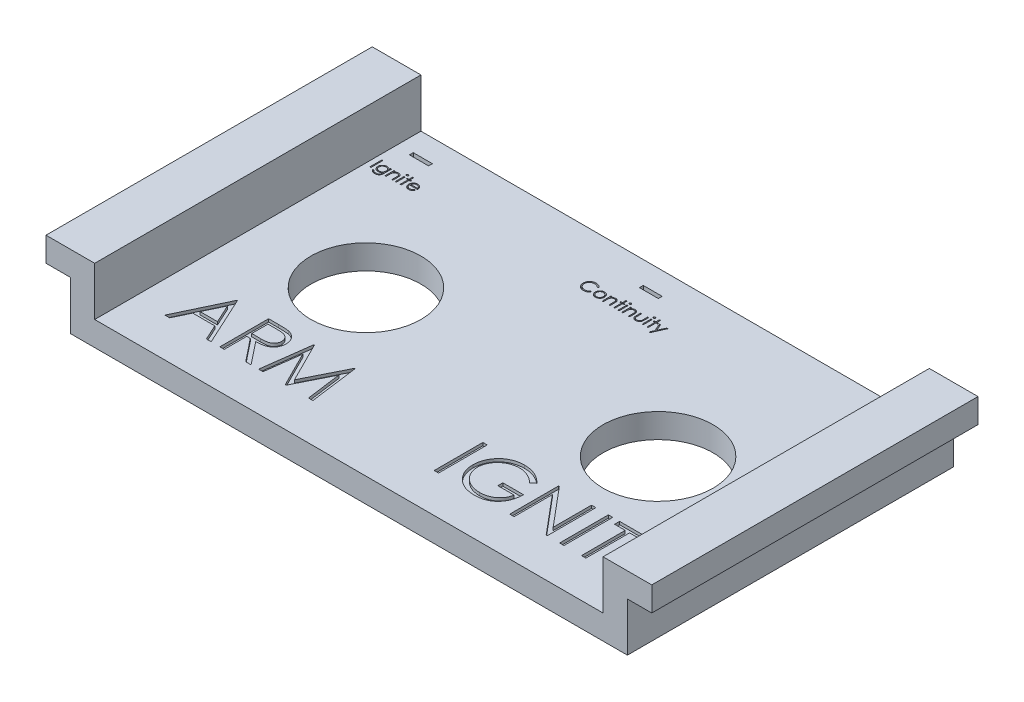
SolidWorks part; units mm, degrees
ref_plane "Front Plane" through (0, 0, 0) normal (0, 0, 1) x (1, 0, 0)
ref_plane "Top Plane" through (0, 0, 0) normal (0, 1, 0) x (1, 0, 0)
ref_plane "Right Plane" through (0, 0, 0) normal (1, 0, 0) x (0, 0, -1)
sketch "Çizim1" plane through (0, 0, 0) normal (0, 1, 0) x (1, 0, 0)
  line L1 (-72.644, -42.545) -> (72.644, -42.545)
  line L2 (-72.644, -42.545) -> (-72.644, 42.545)
  line L3 (-72.644, 42.545) -> (72.644, 42.545)
  line L4 (72.644, -42.545) -> (72.644, 42.545)
  line L5 (-72.644, -42.545) -> (72.644, 42.545) construction
  line L6 (-72.644, 42.545) -> (72.644, -42.545) construction
  point P0 (0, 0)
  dimension "D1" = 145.288
  dimension "D2" = 85.09
extrude "Yükseklik-Ekstrüzyon1" add sketch "Çizim1" along normal blind 6.35
sketch "Çizim2" plane through (-72.644, 0, 0) normal (-1, 0, 0) x (0, 0, 1)
  line L1 (-42.545, 6.35) -> (42.545, 6.35)
  line L2 (-42.545, 6.35) -> (-42.545, 19.05)
  line L3 (-42.545, 19.05) -> (42.545, 19.05)
  line L4 (42.545, 6.35) -> (42.545, 19.05)
  dimension "D1" = 85.09
  dimension "D2" = 12.7
extrude "Yükseklik-Ekstrüzyon2" add sketch "Çizim2" against normal blind 6.35
sketch "Çizim3" plane through (72.644, 0, 0) normal (1, 0, 0) x (0, 0, -1)
  line L1 (-42.545, 6.35) -> (42.545, 6.35)
  line L2 (-42.545, 6.35) -> (-42.545, 19.05)
  line L3 (-42.545, 19.05) -> (42.545, 19.05)
  line L4 (42.545, 6.35) -> (42.545, 19.05)
extrude "Yükseklik-Ekstrüzyon3" add sketch "Çizim3" against normal blind 6.35
sketch "Çizim4" plane through (72.644, 0, 0) normal (1, 0, 0) x (0, 0, -1)
  line L0 (42.545, 19.05) -> (42.545, 0) construction
  line L1 (-42.545, 19.05) -> (42.545, 19.05)
  line L2 (-42.545, 19.05) -> (-42.545, 12.7)
  line L3 (-42.545, 12.7) -> (42.545, 12.7)
  line L4 (42.545, 19.05) -> (42.545, 12.7)
  dimension "D1" = 6.35
sketch "Çizim6" plane through (-72.644, 0, 0) normal (-1, 0, 0) x (0, 0, 1)
  line L1 (-42.545, 19.05) -> (42.545, 19.05)
  line L2 (-42.545, 19.05) -> (-42.545, 12.7)
  line L3 (-42.545, 12.7) -> (42.545, 12.7)
  line L4 (42.545, 19.05) -> (42.545, 12.7)
extrude "Yükseklik-Ekstrüzyon4" add sketch "Çizim6" along normal blind 6.35
extrude "Yükseklik-Ekstrüzyon5" add sketch "Çizim4" along normal blind 6.35
sketch "Çizim7" plane through (0, 6.35, 0) normal (0, 1, 0) x (1, 0, 0)
  circle A0 centre (-38.1, 0) radius 14.351
  dimension "D1" = 28.702
  dimension "D2" = 38.1
extrude "Kes-Ekstrüzyon1" cut sketch "Çizim7" against normal blind 6.35
sketch "Çizim8" plane through (0, 6.35, 0) normal (0, 1, 0) x (1, 0, 0)
  circle A0 centre (38.1, 0) radius 14.351
  dimension "D1" = 28.702
  dimension "D2" = 38.1
extrude "Kes-Ekstrüzyon2" cut sketch "Çizim8" against normal blind 6.35
sketch "Çizim9" plane through (0, 6.35, 0) normal (0, 1, 0) x (1, 0, 0)
  line L0 (66.294, 42.545) -> (-66.294, 42.545) construction
  line L2 (66.294, 42.545) -> (66.294, -42.545) construction
  line L3 (57.944, 36.695) -> (61.944, 36.695)
  line L4 (57.944, 36.695) -> (57.944, 35.695)
  line L5 (57.944, 35.695) -> (61.944, 35.695)
  line L6 (61.944, 36.695) -> (61.944, 35.695)
  line L7 (57.944, 36.695) -> (61.944, 35.695) construction
  line L8 (57.944, 35.695) -> (61.944, 36.695) construction
  point P0 (59.944, 36.195)
  dimension "D1" = 6.35
  dimension "D2" = 6.35
  dimension "D4" = 4
  dimension "D5" = 1
extrude "Kes-Ekstrüzyon3" cut sketch "Çizim9" against normal blind 6.35
sketch "Çizim10" plane through (0, 6.35, 0) normal (0, 1, 0) x (1, 0, 0)
  line L1 (66.294, 42.545) -> (-66.294, 42.545) construction
  line L2 (-2.4613, 36.695) -> (2.4613, 36.695)
  line L3 (-2.4613, 36.695) -> (-2.4613, 35.695)
  line L4 (-2.4613, 35.695) -> (2.4613, 35.695)
  line L5 (2.4613, 36.695) -> (2.4613, 35.695)
  line L6 (-2.4613, 36.695) -> (2.4613, 35.695) construction
  line L7 (-2.4613, 35.695) -> (2.4613, 36.695) construction
  point P0 (0, 36.195)
  dimension "D1" = 1
  dimension "D2" = 6.35
  dimension "D3" = 4.9225
extrude "Kes-Ekstrüzyon4" cut sketch "Çizim10" against normal blind 6.35
sketch "Çizim11" plane through (0, 6.35, 0) normal (0, 1, 0) x (1, 0, 0)
  line L0 (66.294, 42.545) -> (-66.294, 42.545) construction
  text T0 "Continuity"
  dimension "D1" = 14.732
extrude "Kes-Ekstrüzyon5" cut sketch "Çizim11" against normal blind 0.762
sketch "Çizim12" plane through (0, 6.35, 0) normal (0, 1, 0) x (1, 0, 0)
  line L0 (66.294, 42.545) -> (-66.294, 42.545) construction
  text T0 "Radio"
  dimension "D1" = 14.732
extrude "Kes-Ekstrüzyon6" cut sketch "Çizim12" against normal blind 0.762
sketch "Çizim13" plane through (0, 6.35, 0) normal (0, 1, 0) x (1, 0, 0)
  line L0 (-66.294, -42.545) -> (66.294, -42.545) construction
  text T0 "ARM" font "Century Gothic" height 12.7
  dimension "D1" = 10.16
sketch "Çizim14" plane through (0, 6.35, 0) normal (0, 1, 0) x (1, 0, 0)
  line L0 (-66.294, -42.545) -> (66.294, -42.545) construction
  text T0 "IGNITE" font "Century Gothic" height 12.7
  dimension "D1" = 10.16
extrude "Kes-Ekstrüzyon7" cut sketch "Çizim13" against normal blind 0.762
extrude "Kes-Ekstrüzyon8" cut sketch "Çizim14" against normal blind 0.762
sketch "Çizim15" plane through (0, 6.35, 0) normal (0, 1, 0) x (1, 0, 0)
  line L0 (-66.294, -42.545) -> (-66.294, 42.545) construction
  line L2 (66.294, 42.545) -> (-66.294, 42.545) construction
  line L3 (-62.444, 36.695) -> (-57.444, 36.695)
  line L4 (-62.444, 36.695) -> (-62.444, 35.695)
  line L5 (-62.444, 35.695) -> (-57.444, 35.695)
  line L6 (-57.444, 36.695) -> (-57.444, 35.695)
  line L7 (-62.444, 36.695) -> (-57.444, 35.695) construction
  line L8 (-62.444, 35.695) -> (-57.444, 36.695) construction
  point P0 (-59.944, 36.195)
  dimension "D1" = 6.35
  dimension "D2" = 6.35
  dimension "D4" = 1
  dimension "D5" = 5
extrude "Kes-Ekstrüzyon9" cut sketch "Çizim15" against normal blind 6.35
sketch "Çizim16" plane through (0, 6.35, 0) normal (0, 1, 0) x (1, 0, 0)
  line L0 (66.294, 42.545) -> (-66.294, 42.545) construction
  text T0 "Ignite"
  point P1 (-64.8238, 27.813)
  point P4 (0, 0)
  point P5 (-65.3047, 27.813)
  dimension "D1" = 14.732
extrude "Kes-Ekstrüzyon10" cut sketch "Çizim16" against normal blind 0.762
